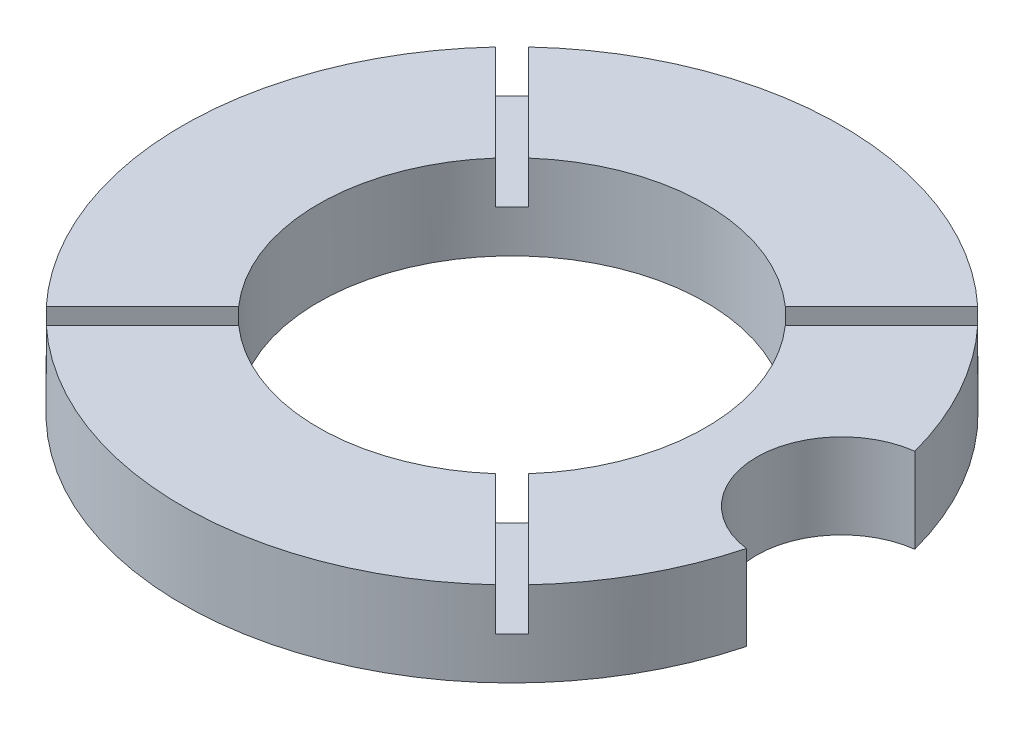
SolidWorks part; units mm, degrees
note: The reader was unsure of these and kept them because the rebuilt part matched: shared geometry of "Sketch1<10>".
ref_plane "Front Plane" through (0, 0, 0) normal (0, 0, 1) x (1, 0, 0)
ref_plane "Top Plane" through (0, 0, 0) normal (0, 1, 0) x (1, 0, 0)
ref_plane "Right Plane" through (0, 0, 0) normal (1, 0, 0) x (0, 0, -1)
sketch "Sketch1" plane through (0, 0, 0) normal (0, 1, 0) x (1, 0, 0)
  circle A0 centre (0, 0) radius 28.9526
  circle A1 centre (0, 0) radius 49.276
  dimension "D1" = 57.9052
  dimension "D2" = 98.552
extrude "Boss-Extrude1" add sketch "Sketch1" along normal blind 12.7 contours A1
extrude "Cut-Extrude2" cut sketch "Sketch1<10>" along normal through all contours A0
sketch "Sketch1<10>" plane through (0, 0, 0) normal (0, 1, 0) x (1, 0, 0) same geometry as "Sketch1"
sketch "Sketch2" plane through (0, 12.7, 0) normal (0, 1, 0) x (1, 0, 0)
  line L1 (0, 0) -> (49.276, 0)
  circle A1 centre (0, 0) radius 49.276 construction
  circle A2 centre (0, 0) radius 49.276
  circle A3 centre (49.276, 0) radius 12.7
  circle M4 centre (0, 0) radius 49.276
  dimension "D1" = 25.4
extrude "Cut-Extrude3" cut sketch "Sketch2" against normal through all contours A3 L1 M4 | L1 A3 M4
sketch "Sketch3" plane through (0, 12.7, 0) normal (0, 1, 0) x (1, 0, 0)
  line L2 (0, 0) -> (-35.921, 35.921) construction
  line L3 (-37.3758, 34.8973) -> (-34.8973, 37.3758)
  line L4 (-37.3758, 34.8973) -> (-19.1998, 16.7212)
  line L5 (-34.8973, 37.3758) -> (-16.7212, 19.1998)
  line L6 (-19.1998, 16.7212) -> (-16.7212, 19.1998)
  line L7 (-37.3758, 34.8973) -> (-16.7212, 19.1998) construction
  line L8 (-34.8973, 37.3758) -> (-19.1998, 16.7212) construction
  line L21 (0, 0) -> (0, 59.8235) construction
  circle A0 centre (0, 0) radius 28.9526 construction
  point P0 (0, 0)
  point P6 (-17.9605, 17.9605)
  point P9 (0, 0)
  point P12 (-27.0485, 27.0485)
  point P13 (-27.0485, 27.0485)
  point P30 (0, 0.354)
  point P31 (-4.3236, 4.5408)
  arc M18 (47.6394, 12.5941) -> (47.6394, -12.5941) centre (0, 0) ccw
  circle M19 centre (0, 0) radius 28.9526
  dimension "D2" = 3.5052
  dimension "D3" = 51.1048
  dimension "D1" = 45
  dimension "D4" = 25.4
extrude "Cut-Extrude4" cut sketch "Sketch3" against normal blind 6.35 contours L5 L4 M18 M19 | L4 L6 L5 M19 | L5 L3 L4 M18
pattern_circular "CirPattern1" count 4 over 360 about axis through (0, 0, 0) along (0, 1, 0) of "Cut-Extrude4"
ref_plane "Plane1" through (0, 6.35, 0) normal (0, 1, 0) x (1, 0, 0)
equation "\"Motor_OD\" = 54.4mm"
equation "\"Aft_Section_Length\" = 32in"
equation "\"Mid_Coupler_Length\" = 12in"
equation "\"AB_Coupler_OD_Length\"= 1in"
equation "\"AB_Coupling_Section_Length\"= 0.375in"
equation "\"AB_Coupler_Length\"= \"AB_Coupler_OD_Length\" + \"AB_Coupling_Section_Length\" * 2"
equation "\"Cutout_Angle\" = 60"
equation "\"AB_Paddle_Height\" = 0.375in"
equation "\"AB_Coupler_Num_Screws\"= 4"
equation "\"Num_Cutouts\" = 4"
equation "\"AB_Coupler_OD\"= 4.024in"
equation "\"AB_Coupler_ID\"= 3.7in"
equation "\"AB_Coupler_Surface_Diameter\"= 3.899in"
equation "\"AB_Coupling_Screw_Diameter\"= 0.1065in"
equation "\"AB_Central_Bushing_Length\" = 0.75in"
equation "\"Lead_Screw_Dist\" = 2in"
equation "\"Lead_Screw_Diam\" = 0.375in"
equation "\"Lead_Screw_Length\" = \"Mid_Coupler_Length\" + 2*0.375in + 2*0.5in"
equation "\"Paddle_Pin_Offset\" = 0.25in"
equation "\"Paddle_Pin_Radius\" = 2.25*2/3in"
equation "\"Paddle_Gear_OD\" = 3.2in"
equation "\"Fwd_BKHD_From_Top\" = 18in"
equation "\"D1@Sketch1\" = \"Motor_OD\" + .02 + 0.118"
equation "\"Fin_Thickness\"= .118in"
equation "\"Guiderail_Cutout_Diameter\"= 1.5in"
equation "\"D2@Sketch3\" = \"Fin_Thickness\" + 0.02"
equation "\"D1@Sketch2\" = \"Centering_Ring_Cutout_Dia\""
equation "\"Motor_Length\" = 401mm"
equation "\"Body_Tube_OD\"= 4.024in"
equation "\"Body_Tube_ID\"= 3.90in"
equation "\"Coupler_OD\" = 3.899in"
equation "\"Coupler_ID\" = 3.755in"
equation "\"Fwd_Section_Length\" = 20in"
equation "\"Mid_Section_Length\" = 4in"
equation "\"Aft_Upper_Tube_Length\" = 10in"
equation "\"Aft_Lower_Tube_Length\" = 18in"
equation "\"Nosecone_Coupler_Length\" = 5in"
equation "\"Avionics_Bulkhead_Thickness\" = 0.25in"
equation "\"Avionics_Bulkhead_Lip\" = 0.125in"
equation "\"Avionics_Board_Length\" = \"Mid_Coupler_Length\" - 2*\"Avionics_Bulkhead_Lip\""
equation "\"Lead_Screw_Hole_Diam\" = 0.386in"
equation "\"Centering_Ring_Cutout_Dia\"= 1in"
equation "\"D2@Sketch1\"= \"Body_Tube_ID\" - 0.02"
equation "\"D3@Sketch3\"=\"Body_Tube_OD\"/2"
